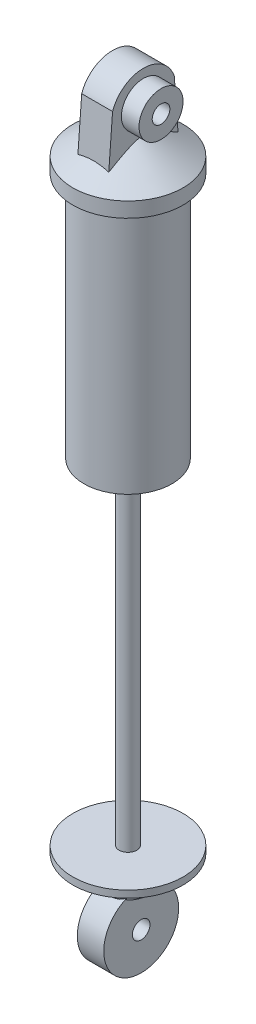
SolidWorks part; units mm, degrees
ref_plane "Front Plane" through (0, 0, 0) normal (0, 0, 1) x (1, 0, 0)
ref_plane "Top Plane" through (0, 0, 0) normal (0, 1, 0) x (1, 0, 0)
ref_plane "Right Plane" through (0, 0, 0) normal (1, 0, 0) x (0, 0, -1)
sketch "Sketch1" plane through (0, 0, 0) normal (0, 1, 0) x (1, 0, 0)
  circle A0 centre (0, 0) radius 7.9375
  dimension "D1" = 15.875
extrude "Extrude1" add sketch "Sketch1" against normal blind 86.995
ref_plane "Plane1" through (0, 3.937, 0) normal (0, 1, 0) x (-1, 0, 0)
sketch "Sketch3" plane through (0, 3.937, 0) normal (0, 1, 0) x (-1, 0, 0)
  circle A0 centre (0, 0) radius 1.905
  dimension "D1" = 3.81
loft "Loft1" add profiles "Sketch1<2>", "Sketch3" connector at (3.2072, 0, 7.2607) connector at (0.0754, 3.937, 1.9035)
sketch "Sketch1<2>" plane through (0, 0, 0) normal (0, 1, 0) x (1, 0, 0) same geometry as "Sketch1"
sketch "Sketch4" plane through (0, 0, 0) normal (1, 0, 0) x (0, 0, -1)
  line L0 (-4.9656, 1.905) -> (4.9656, 1.905) construction
  line L1 (4.9656, 1.905) -> (4.445, 8.89)
  line L2 (0, 12.065) -> (4.9656, 12.065) construction
  line L3 (-4.445, 8.89) -> (-4.9656, 1.905)
  line L4 (0, 0) -> (0, 9.4629) construction
  line L5 (-4.9656, 1.905) -> (-5.1076, 0)
  line L6 (7.9375, 0) -> (-7.9375, 0) construction
  line L7 (4.9656, 1.905) -> (5.1076, 0)
  line L8 (5.1076, 0) -> (-5.1076, 0)
  line L10 (-1.27, 6.35) -> (1.27, 6.35) construction
  line L11 (-1.27, 6.35) -> (-1.27, 8.89) construction
  line L12 (-1.27, 8.89) -> (1.27, 8.89) construction
  line L13 (1.27, 6.35) -> (1.27, 8.89) construction
  line L14 (-1.27, 6.35) -> (1.27, 8.89) construction
  line L15 (-1.27, 8.89) -> (1.27, 6.35) construction
  arc A0 (-4.445, 8.89) -> (4.445, 8.89) centre (0, 7.366) cw
  circle A1 centre (0, 7.62) radius 1.27
  spline S0 degree 3 poles (-1.905, 3.937) (-1.9298, 3.9193) (-1.963, 3.8954) (-2.003, 3.867) (-2.0531, 3.8315) (-2.1087, 3.7925) (-2.2033, 3.7265) (-2.2759, 3.6762) (-2.3922, 3.5963) (-2.475, 3.5398) (-2.579, 3.4693) (-2.6662, 3.4104) (-2.7586, 3.3483) (-2.8555, 3.2835) (-2.9745, 3.204) (-3.1326, 3.0991) (-3.37, 2.9424) (-3.5551, 2.8209) (-3.7198, 2.7132) (-3.826, 2.6438) (-3.9668, 2.552) (-4.1229, 2.4504) (-4.2648, 2.3583) (-4.3988, 2.2714) (-4.5561, 2.1695) (-4.7194, 2.0639) (-4.8575, 1.9747) (-5.0644, 1.8412) (-5.2722, 1.7074) (-5.5334, 1.5394) (-5.7601, 1.3937) (-6.0463, 1.21) (-6.4025, 0.9816) (-6.7879, 0.7348) (-7.1542, 0.5005) (-7.414, 0.3344) (-7.6599, 0.1773) (-7.8134, 0.0793) (-7.9375, 0) knots 0 0 0 0 0.012685 0.017018 0.020445 0.03826 0.045291 0.068488 0.075025 0.104079 0.110205 0.127331 0.14794 0.156552 0.175873 0.207562 0.235559 0.294302 0.299794 0.317492 0.347152 0.369783 0.395042 0.417599 0.436317 0.473091 0.498532 0.504794 0.575636 0.60146 0.634088 0.687922 0.743056 0.810289 0.878494 0.92414 0.938684 1 1 1 1 construction
  spline S1 degree 3 poles (7.9375, 0) (7.8257, 0.0714) (7.6722, 0.1694) (7.5036, 0.2772) (7.3066, 0.4031) (6.9555, 0.6275) (6.4286, 0.9648) (5.9657, 1.2616) (5.6639, 1.4555) (5.5129, 1.5525) (5.3908, 1.6311) (5.2417, 1.727) (5.0781, 1.8325) (4.9585, 1.9096) (4.8941, 1.9511) (4.7939, 2.0158) (4.633, 2.1197) (4.472, 2.224) (4.3176, 2.324) (4.1478, 2.4342) (3.9473, 2.5646) (3.7978, 2.6622) (3.7128, 2.7177) (3.6411, 2.7646) (3.5677, 2.8127) (3.4747, 2.8737) (3.3779, 2.9373) (3.2891, 2.9957) (3.2048, 3.0512) (3.1255, 3.1037) (3.0458, 3.1567) (2.9673, 3.2089) (2.8929, 3.2585) (2.8394, 3.2942) (2.7934, 3.325) (2.733, 3.3655) (2.6476, 3.4229) (2.5621, 3.4807) (2.4783, 3.5376) (2.4054, 3.5873) (2.336, 3.6349) (2.2544, 3.6911) (2.1808, 3.7421) (2.0885, 3.8066) (2.0336, 3.8453) (1.966, 3.8933) (1.932, 3.9177) (1.905, 3.937) knots 0 0 0 0 0.055193 0.075764 0.083269 0.152469 0.24918 0.343561 0.381249 0.39843 0.418269 0.441638 0.472216 0.499267 0.500879 0.504047 0.549312 0.580095 0.584151 0.625871 0.664303 0.683667 0.700174 0.706544 0.71932 0.736702 0.752813 0.767763 0.781713 0.794826 0.807252 0.822002 0.834734 0.844578 0.84877 0.857738 0.874872 0.891566 0.90071 0.917004 0.928262 0.935737 0.958237 0.965513 0.982582 0.986185 1 1 1 1 construction
  dimension "D5" = 2.54
  dimension "D1" = 1.905
  dimension "D2" = 8.89
  dimension "D3" = 6.985
  dimension "D4" = 3.175
  dimension "D6" = 3.175
extrude "Extrude2" add sketch "Sketch4" along normal mid plane 4.445
sketch "Sketch5" plane through (0, 0, 0) normal (1, 0, 0) x (0, 0, -1)
  line L0 (0, -86.995) -> (0, -100.965) construction
  line L1 (-7.9375, -86.995) -> (7.9375, -86.995) construction
  circle A0 centre (0, -95.5675) radius 5.3975
  circle A1 centre (0, -95.5675) radius 1.27
  dimension "D2" = 10.795
  dimension "D3" = 2.54
  dimension "D1" = 13.97
extrude "Extrude3" add sketch "Sketch5" along normal mid plane 3.81 separate body
sketch "Sketch6" plane through (0, -86.995, 0) normal (0, -1, 0) x (1, 0, 0)
  circle A0 centre (0, 0) radius 4.1275
  dimension "D1" = 8.255
extrude "Extrude4" add sketch "Sketch6" along normal blind 1.905
sketch "Sketch7" plane through (0, -88.9, 0) normal (0, -1, 0) x (1, 0, 0)
  circle A0 centre (0, 0) radius 2.8575
  dimension "D1" = 5.715
extrude "Extrude5" add sketch "Sketch7" along normal blind 1.905
sketch "Sketch8" plane through (2.2225, 0, 0) normal (1, 0, 0) x (0, 0, -1)
  circle A0 centre (0, 7.62) radius 3.175
  circle A1 centre (0, 7.62) radius 1.27
  circle A2 centre (0, 7.62) radius 1.27 construction
  dimension "D1" = 6.35
extrude "Extrude6" add sketch "Sketch8" along normal blind 2.54
ref_plane "Plane2" through (0, -2.159, 0) normal (0, 1, 0) x (-1, 0, 0)
sketch "Sketch10" plane through (0, -2.159, 0) normal (0, 1, 0) x (-1, 0, 0)
  circle A0 centre (0, 0) radius 6.35
  circle A1 centre (0, 0) radius 7.9375
  dimension "D1" = 12.7
  dimension "D2" = 15.875
extrude "Cut-Extrude2" cut sketch "Sketch10" against normal blind 38.1
ref_plane "Plane3" through (0, -37.719, 0) normal (0, 1, 0) x (-1, 0, 0)
sketch "Sketch11" plane through (0, -37.719, 0) normal (0, 1, 0) x (-1, 0, 0)
  circle A0 centre (0, 0) radius 1.27
  circle A1 centre (0, 0) radius 7.9375
  dimension "D1" = 2.54
  dimension "D2" = 15.875
extrude "Cut-Extrude3" cut sketch "Sketch11" against normal blind 48.26
